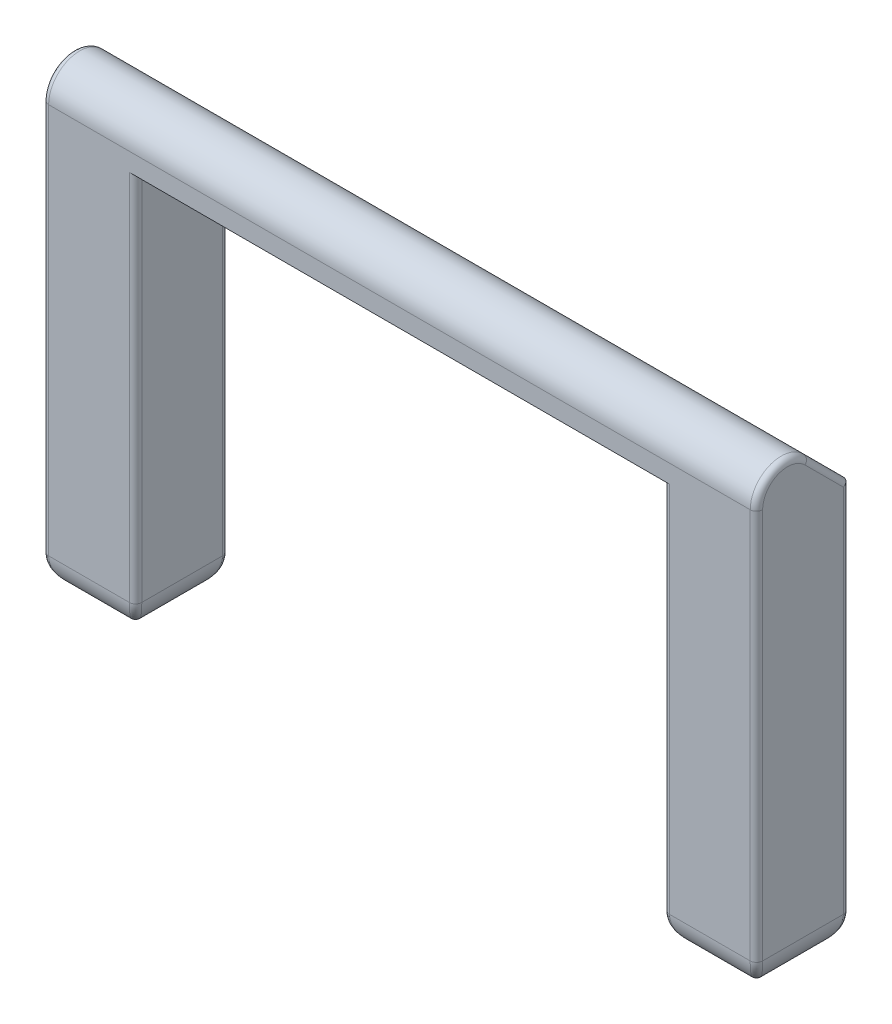
SolidWorks part; units mm, degrees
material "ABS"
ref_plane "前视基准面" through (0, 0, 0) normal (0, 0, 1) x (1, 0, 0)
ref_plane "上视基准面" through (0, 0, 0) normal (0, 1, 0) x (1, 0, 0)
ref_plane "右视基准面" through (0, 0, 0) normal (1, 0, 0) x (0, 0, -1)
sketch "草图1" plane through (0, 0, 0) normal (0, 1, 0) x (1, 0, 0)
  line L0 (0, 0) -> (0, 12.1875) construction
  line L1 (-11.5, -1.5) -> (-8.5, -1.5)
  line L2 (-11.5, -1.5) -> (-11.5, 1.5)
  line L3 (-11.5, 1.5) -> (-8.5, 1.5)
  line L4 (-8.5, -1.5) -> (-8.5, 1.5)
  line L5 (-11.5, -1.5) -> (-8.5, 1.5) construction
  line L6 (-11.5, 1.5) -> (-8.5, -1.5) construction
  line L7 (11.5, 1.5) -> (8.5, -1.5) construction
  line L8 (11.5, -1.5) -> (8.5, 1.5) construction
  line L9 (8.5, -1.5) -> (8.5, 1.5)
  line L10 (11.5, 1.5) -> (8.5, 1.5)
  line L11 (11.5, -1.5) -> (11.5, 1.5)
  line L12 (11.5, -1.5) -> (8.5, -1.5)
  point P0 (-10, 0)
  point P13 (10, 0)
  dimension "D1" = 10
  dimension "D2" = 3
  dimension "D3" = 3
extrude "凸台-拉伸1" add sketch "草图1" along normal blind 13
sketch "草图3" plane through (-11.5, 0, 0) normal (-1, 0, 0) x (0, 0, 1)
  line L0 (1.5, 13) -> (-0.9879, 10.5121)
  line L1 (-1.5, 13) -> (-1.5, 0) construction
  line L2 (-1.5, 13) -> (1.5, 13) construction
  line L3 (-1.5, 10.7243) -> (-1.5, 13)
  line L4 (-1.5, 13) -> (-0.2071, 14.2929)
  line L5 (1.5, 13.5858) -> (1.5, 13)
  arc A0 (-0.2071, 14.2929) -> (1.5, 13.5858) centre (0.5, 13.5858) cw
  arc A1 (-0.9879, 10.5121) -> (-1.5, 10.7243) centre (-1.2, 10.7243) cw
  point P14 (-1.5, 10)
  dimension "D3" = 1
  dimension "D4" = 0.3
  dimension "D1" = 45
  dimension "D2" = 45
extrude "凸台-拉伸2" add sketch "草图3" against normal up to surface (23 mm away) up to face at (11.5, 6.5, 0)
fillet "圆角1" radius 1 8 edges at (-10, 0, -1.5) (-11.5, 0, 0) (-10, 0, 1.5) (-8.5, 0, 0) (10, 0, -1.5) (8.5, 0, 0) (10, 0, 1.5) (11.5, 0, 0)
fillet "圆角2" radius 0.2 20 edges at (-11.2071, 0.2929, -1.2071) (-11.5, 13.6464, -0.8536) (-11.5, 14.5097, 0.8827) (-11.2071, 0.2929, 1.2071) (-8.7929, 0.2929, 1.2071) (-8.7929, 0.2929, -1.2071) (8.7929, 0.2929, 1.2071) (8.7929, 0.2929, -1.2071) (11.5, 13.6464, -0.8536) (11.5, 14.5097, 0.8827) (11.2071, 0.2929, 1.2071) (11.2071, 0.2929, -1.2071) (-11.5, 7, -1.5) (-11.5, 7.2929, 1.5) (-8.5, 7, 1.5) (-8.5, 5.8621, -1.5) (8.5, 7, 1.5) (8.5, 5.8621, -1.5) (11.5, 7.2929, 1.5) (11.5, 7, -1.5)
